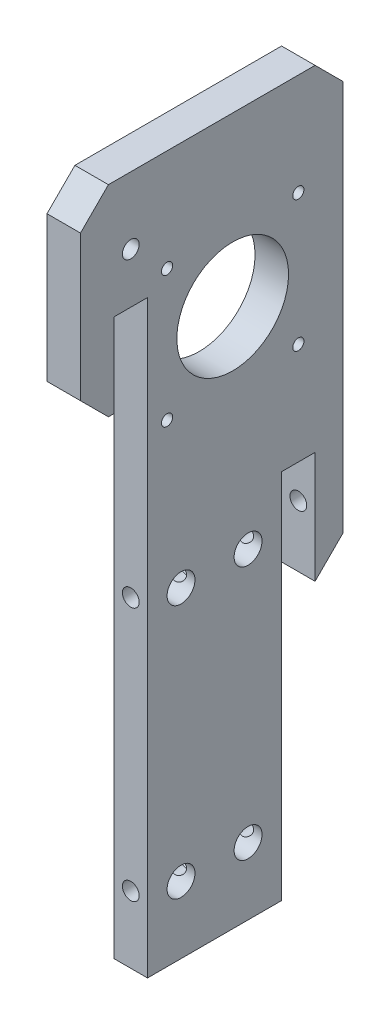
SolidWorks part; units mm, degrees
material "HDPE-green"
ref_plane "Front Plane" through (0, 0, 0) normal (0, 0, 1) x (1, 0, 0)
ref_plane "Top Plane" through (0, 0, 0) normal (0, 1, 0) x (1, 0, 0)
ref_plane "Right Plane" through (0, 0, 0) normal (1, 0, 0) x (0, 0, -1)
sketch "Sketch1" plane through (0, 0, 0) normal (1, 0, 0) x (0, 0, -1)
  line L1 (-29.5, 60) -> (29.5, 60)
  line L2 (-29.5, 60) -> (-29.5, -60)
  line L3 (-29.5, -60) -> (29.5, -60)
  line L4 (29.5, 60) -> (29.5, -60)
  line L5 (-29.5, 60) -> (29.5, -60) construction
  line L6 (-29.5, -60) -> (29.5, 60) construction
  circle A0 centre (0, 0) radius 20
  point P0 (0, 0)
  dimension "D3" = 40
  dimension "D1" = 59
  dimension "D2" = 120
extrude "Boss-Extrude1" add sketch "Sketch1" along normal blind 12
hole_wizard "Ø4.0 (4) Diameter Hole1" positions "Sketch5" profile "Sketch4" hole size "Ø4.0" standard "ISO" end condition up to next
sketch "Sketch5" plane through (0, 0, 0) normal (-1, 0, 0) x (0, 0, 1)
  point P0 (-23.5, 23.5)
  point P1 (23.5, 23.5)
  point P3 (23.5, -23.5)
  point P5 (-23.5, -23.5)
  dimension "D1" = 23.5
  dimension "D2" = 23.5
  dimension "D3" = 23.5
  dimension "D4" = 23.5
  dimension "D5" = 23.5
  dimension "D6" = 23.5
  dimension "D7" = 23.5
  dimension "D8" = 23.5
sketch "Sketch4" plane through (0, 23.5, -23.5) normal (0, 1, 0) x (0, 0, 1)
  line L0 (0, 0) -> (0, 12)
  line L1 (0, 12) -> (2, 12)
  line L2 (2, 12) -> (2, 0)
  line L5 (2, 0) -> (0, 0)
  line L11 (0, -6.35) -> (0, 107.95) construction
  dimension "Thru Hole Dia." = 4
  dimension "Thru Hole Depth" = 12
hole_wizard "Hole1" positions "Sketch7" profile "Sketch6" legacy
sketch "Sketch7" plane through (0, 0, 0) normal (-1, 0, 0) x (0, 0, 1)
  line L0 (0, -57.2998) -> (0, 35.7294) construction
  point P0 (0, 45)
  point P1 (0, -45)
  dimension "D1" = 45
  dimension "D2" = 45
sketch "Sketch6" plane through (0, 45, 0) normal (0, 1, 0) x (0, 0, 1)
  line L0 (0, 0) -> (0, 6)
  line L1 (0, 6) -> (6, 6)
  line L2 (6, 6) -> (6, 0)
  line L5 (6, 0) -> (0, 0)
  line L11 (0, -6.35) -> (0, 107.95) construction
  dimension "Thru Hole Dia." = 12
  dimension "Thru Hole Depth" = 6
sketch "Sketch8" plane through (0, 0, 0) normal (-1, 0, 0) x (0, 0, 1)
  line L2 (42.5, 18) -> (42.5, -12)
  line L3 (42.5, -12) -> (54.5, -12)
  line L4 (54.5, -12) -> (54.5, 60)
  line L5 (54.5, 60) -> (29.5, 60)
  line L7 (29.5, 60) -> (29.5, -60)
  line L9 (29.5, -60) -> (30.5, -60)
  line L10 (30.5, -60) -> (30.5, 18)
  line L11 (30.5, 18) -> (42.5, 18)
  dimension "D1" = 72
  dimension "D2" = 1
  dimension "D3" = 12
  dimension "D4" = 30
extrude "Boss-Extrude2" add sketch "Sketch8" against normal blind 12
sketch "Sketch9" plane through (0, 0, 0) normal (-1, 0, 0) x (0, 0, 1)
  line L0 (-29.5, -60) -> (-29.5, 60) construction
  line L1 (30.5, -60) -> (-17.5, -60)
  line L2 (30.5, -60) -> (30.5, -193)
  line L3 (30.5, -193) -> (-17.5, -193)
  line L4 (-17.5, -60) -> (-17.5, -193)
  dimension "D1" = 12
  dimension "D2" = 133
  dimension "D3" = 48
extrude "Boss-Extrude3" add sketch "Sketch9" against normal blind 12
sketch "Sketch11" plane through (12, 0, 0) normal (1, 0, 0) x (0, 0, -1)
  line L1 (29.5, 60) -> (39.5, 60)
  line L2 (29.5, 60) -> (29.5, -100)
  line L3 (29.5, -100) -> (39.5, -100)
  line L4 (39.5, 60) -> (39.5, -100)
  dimension "D1" = 10
  dimension "D2" = 160
extrude "Boss-Extrude4" add sketch "Sketch11" against normal blind 12
chamfer "Chamfer1" distance 10 angle 45 3 edges at (6, 60, -39.5) (6, 60, 54.5) (6, -12, 54.5)
chamfer "Chamfer2" distance 10 angle 45 1 edges at (6, -100, -39.5)
hole_wizard "Ø10.0 (10) Diameter Hole1" positions "Sketch14" profile "Sketch13" hole size "Ø10.0" standard "ISO" end condition up to next
sketch "Sketch14" plane through (12, 0, 0) normal (1, 0, 0) x (0, 0, -1)
  line L0 (17.5, -193) -> (-30.5, -193) construction
  line L2 (17.5, -60) -> (17.5, -193) construction
  line L3 (-30.5, -193) -> (-30.5, 18) construction
  point P0 (-18.5, -169)
  point P1 (5.5, -169)
  point P3 (-18.5, -78)
  point P13 (5.5, -78)
  dimension "D1" = 24
  dimension "D2" = 24
  dimension "D3" = 12
  dimension "D4" = 12
  dimension "D5" = 12
  dimension "D6" = 12
  dimension "D7" = 115
  dimension "D8" = 115
sketch "Sketch13" plane through (12, -169, 18.5) normal (0, 1, 0) x (0, 0, -1)
  line L0 (0, 0) -> (0, 12)
  line L1 (0, 12) -> (5, 12)
  line L2 (5, 12) -> (5, 0)
  line L5 (5, 0) -> (0, 0)
  line L11 (0, -6.35) -> (0, 107.95) construction
  dimension "Thru Hole Dia." = 10
  dimension "Thru Hole Depth" = 12
hole_wizard "Ø6.0 (6) Diameter Hole1" positions "Sketch16" profile "Sketch15" hole size "Ø6.0" standard "ISO"
sketch "Sketch16" plane through (0, 0, -17.5) normal (0, 0, -1) x (-1, 0, 0)
  line L0 (-12, -60) -> (-12, -193) construction
  line L2 (-12, -193) -> (0, -193) construction
  point P0 (-6, -169)
  point P7 (-6, -78)
  dimension "D1" = 6
  dimension "D2" = 24
  dimension "D3" = 115
sketch "Sketch15" plane through (6, -169, -17.5) normal (1, 0, 0) x (0, 1, 0)
  line L0 (0, 0) -> (0, 21.8026)
  line L1 (0, 21.8026) -> (3, 20)
  line L2 (3, 20) -> (3, 0)
  line L5 (3, 0) -> (0, 0)
  line L10 (0, 21.8026) -> (-3, 20) construction
  line L11 (0, -6.35) -> (0, 107.95) construction
  dimension "Hole Dia." = 6
  dimension "Hole Depth" = 20
  dimension "Drill Angle" = 118
hole_wizard "Ø6.0 (6) Diameter Hole3" positions "Sketch20" profile "Sketch19" hole size "Ø6.0" standard "ISO"
sketch "Sketch20" plane through (0, 0, -39.5) normal (0, 0, -1) x (-1, 0, 0)
  line L0 (-12, -90) -> (-12, 50) construction
  line L1 (-12, -193) -> (0, -193) construction
  point P0 (-6, -78)
  dimension "D1" = 6
  dimension "D2" = 115
sketch "Sketch19" plane through (6, -78, -39.5) normal (1, 0, 0) x (0, 1, 0)
  line L0 (0, 0) -> (0, 21.8026)
  line L1 (0, 21.8026) -> (3, 20)
  line L2 (3, 20) -> (3, 0)
  line L5 (3, 0) -> (0, 0)
  line L10 (0, 21.8026) -> (-3, 20) construction
  line L11 (0, -6.35) -> (0, 107.95) construction
  dimension "Hole Dia." = 6
  dimension "Hole Depth" = 20
  dimension "Drill Angle" = 118
hole_wizard "Ø6.0 (6) Diameter Hole4" positions "Sketch22" profile "Sketch21" hole size "Ø6.0" standard "ISO" end condition up to next
sketch "Sketch22" plane through (12, 0, 0) normal (1, 0, 0) x (0, 0, -1)
  line L1 (29.5, 60) -> (-44.5, 60) construction
  line L2 (-30.5, -193) -> (-30.5, 18) construction
  point P0 (-36.5, 36)
  dimension "D1" = 6
  dimension "D2" = 24
sketch "Sketch21" plane through (12, 36, 36.5) normal (0, 1, 0) x (0, 0, -1)
  line L0 (0, 0) -> (0, 12)
  line L1 (0, 12) -> (3, 12)
  line L2 (3, 12) -> (3, 0)
  line L5 (3, 0) -> (0, 0)
  line L11 (0, -6.35) -> (0, 107.95) construction
  dimension "Thru Hole Dia." = 6
  dimension "Thru Hole Depth" = 12
hole_wizard "Ø6.0 (6) Diameter Hole5" positions "Sketch24" profile "Sketch23" hole size "Ø6.0" standard "ISO"
sketch "Sketch24" plane through (0, 0, 30.5) normal (0, 0, 1) x (1, 0, 0)
  line L0 (12, -193) -> (0, -193) construction
  line L1 (12, -193) -> (12, 18) construction
  point P0 (6, -78)
  point P1 (6, -169)
  point P12 (10.5332, -82.6225)
  point P17 (8.3323, -81.3658)
  dimension "D1" = 24
  dimension "D2" = 6
  dimension "D3" = 115
  dimension "D4" = 6
sketch "Sketch23" plane through (6, -78, 30.5) normal (1, 0, 0) x (0, -1, 0)
  line L0 (0, 0) -> (0, 21.8026)
  line L1 (0, 21.8026) -> (3, 20)
  line L2 (3, 20) -> (3, 0)
  line L5 (3, 0) -> (0, 0)
  line L10 (0, 21.8026) -> (-3, 20) construction
  line L11 (0, -6.35) -> (0, 107.95) construction
  dimension "Hole Dia." = 6
  dimension "Hole Depth" = 20
  dimension "Drill Angle" = 118
